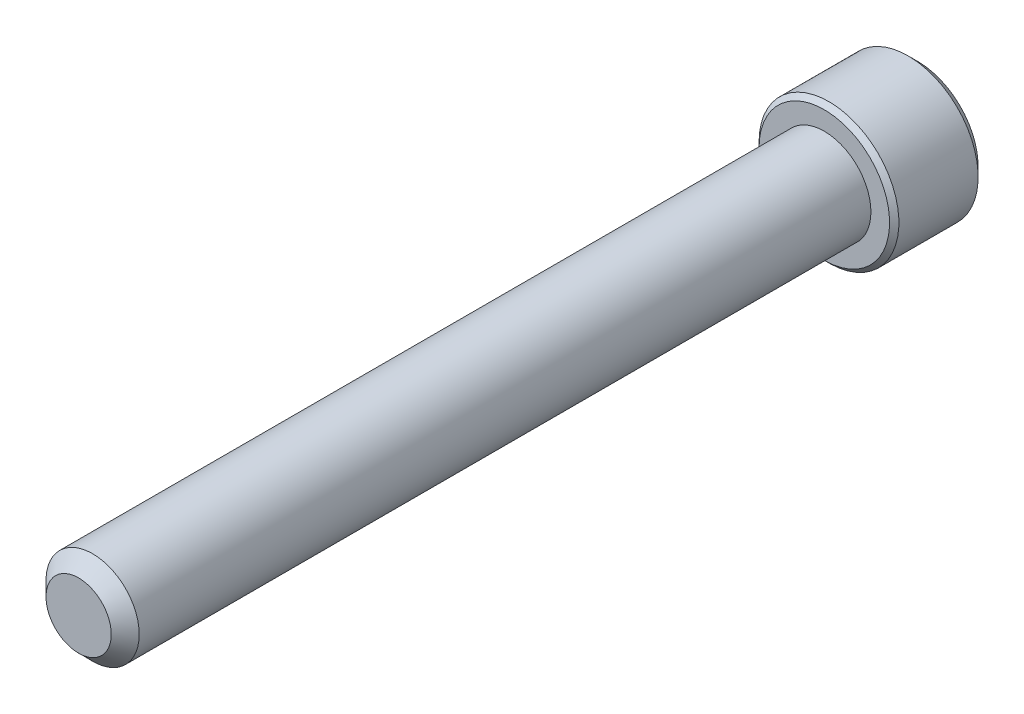
SolidWorks part; units mm, degrees
material "AISI 304"
ref_plane "Front Plane" through (0, 0, 0) normal (0, 0, 1) x (1, 0, 0)
ref_plane "Top Plane" through (0, 0, 0) normal (0, 1, 0) x (1, 0, 0)
ref_plane "Right Plane" through (0, 0, 0) normal (1, 0, 0) x (0, 0, -1)
sketch "Sketch1" plane through (0, 0, 0) normal (0, 0, 1) x (1, 0, 0)
  line L0 (0, 3.175) -> (0, -3.175) construction
  circle A0 centre (0, 0) radius 3.175
  dimension "OD" = 6.35
extrude "Extrude1" add sketch "Sketch1" against normal blind 50.8
sketch "Sketch2" plane through (0, 0, 0) normal (0, 0, 1) x (1, 0, 0)
  circle A0 centre (0, 0) radius 3.175 construction
  circle A1 centre (0, 0) radius 3.175
curve "Helix/Spiral1" pitch 1.27 height 27.94 turns 22 parameters "pitch"=1.27
chamfer "Chamfer3" distance 0.9525 angle 45 1 edges at (3.175, 0, 0)
sketch "Sketch3" plane through (0, 0, 0) normal (1, 0, 0) x (0, 0, -1)
  line L0 (-1.1112, 3.175) -> (-0.635, 2.3501)
  line L1 (-0.635, 2.3501) -> (-0.4763, 2.3501)
  line L2 (-0.4763, 2.3501) -> (0, 3.175)
  line L3 (-1.1112, 3.175) -> (0, 3.175)
  line L4 (-0.5556, 3.175) -> (-0.5556, 2.3501) construction
  line L5 (-0.8731, 2.7626) -> (-0.2381, 2.7626) construction
  line L6 (0, 3.175) -> (0, -3.175) construction
  dimension "D1" = 0.1588
  dimension "D2" = 0.635
  dimension "D3" = 60
sweep "Cut-Sweep1" [suppressed] cut profiles "Sketch3" path "Helix/Spiral1"
sketch "Sketch5" plane through (0, 0, 0) normal (1, 0, 0) x (0, 0, -1)
  line L1 (50.8, 3.175) -> (25.4, 3.175)
  line L2 (50.8, 3.175) -> (50.8, 0)
  line L3 (50.8, 0) -> (25.4, 0)
  line L4 (25.4, 3.175) -> (25.4, 0) construction
  line L6 (0, 0) -> (9.9695, 0) construction
  line L8 (25.4, 3.175) -> (22.225, 0)
  line L9 (22.225, 0) -> (25.4, 0)
  line L10 (50.8, -3.175) -> (50.8, 3.175) construction
  dimension "Thread min" = 25.4
  dimension "D1" = 45
revolve "partially thread" add sketch "Sketch5" angle 360 about L6
sketch "Sketch6" plane through (0, 0, -50.8) normal (0, 0, -1) x (-1, 0, 0)
  circle A0 centre (0, 0) radius 4.7625
  dimension "head dia" = 9.525
extrude "Extrude2" add sketch "Sketch6" along normal blind 6.35
sketch "Sketch7" plane through (0, 0, -57.15) normal (0, 0, -1) x (-1, 0, 0)
  line L1 (0, 2.7496) -> (-2.3812, 1.3748)
  line L2 (-2.3812, 1.3748) -> (-2.3813, -1.3748)
  line L3 (-2.3813, -1.3748) -> (0, -2.7496)
  line L4 (0, -2.7496) -> (2.3813, -1.3748)
  line L5 (2.3813, -1.3748) -> (2.3813, 1.3748)
  line L6 (2.3813, 1.3748) -> (0, 2.7496)
  circle A0 centre (0, 0) radius 2.3813 construction
  dimension "hex dia" = 4.7625
extrude "Cut-Extrude1" cut sketch "Sketch7" against normal blind 3.5719
sketch "Sketch8" plane through (0, 0, -57.15) normal (0, 0, -1) x (-1, 0, 0)
  circle A0 centre (0, 0) radius 2.7496
extrude "Cut-Extrude2" cut sketch "Sketch8" against normal blind 0.635 draft 45
chamfer "Chamfer1" distance 0.635 angle 45 1 edges at (-4.7625, 0, -57.15)
chamfer "Chamfer2" distance 0.3175 angle 45 1 edges at (-4.7625, 0, -50.8)
sketch "Sketch9" plane through (0, 0, 0) normal (1, 0, 0) x (0, 0, -1)
  line L0 (0, 3.175) -> (0, -3.175) construction
  line L1 (6.985, 3.175) -> (6.985, -3.175) construction
  line L2 (50.8, 4.7625) -> (50.8, -4.7625) construction
  line L3 (57.15, 4.7625) -> (57.15, -4.7625) construction
  line L4 (57.15, 0) -> (0, 0) construction
  line L5 (61.6852, 3.175) -> (61.6852, -3.175) construction
  dimension "D1" = 6.985
  dimension "D2" = 6.35
  dimension "D3" = 9.525
  dimension "D4" = 50.8
  dimension "Thread Length" = 61.6852
equation "\"D3@Helix/Spiral1\" = \"Thread min@Sketch5\"+(\"pitch@Helix/Spiral1\"*2)"
equation "\"D1@Sketch3\" = \"pitch@Helix/Spiral1\"*.125"
equation "\"D2@Sketch3\" = \"pitch@Helix/Spiral1\"*.5"
equation "\"D1@Cut-Extrude1\" = \"hex dia@Sketch7\"*.75"
equation "\"D1@Chamfer1\" = \"head depth@Extrude2\"/10"
equation "\"D1@Sketch9\" = \"pitch@Helix/Spiral1\"*5.5"
equation "\"D1@Chamfer2\" = \"D1@Chamfer1\"/2"
equation "\"D1@Cut-Extrude2\" = \"D1@Chamfer2\"*2"
equation "\"D1@Chamfer3\" = \"pitch@Helix/Spiral1\"*.750"
equation "\"D2@Sketch9\" = \"head depth@Extrude2\""
equation "\"D3@Sketch9\" = \"head dia@Sketch6\""
equation "\"D4@Sketch9\" = \"screw length@Extrude1\""
